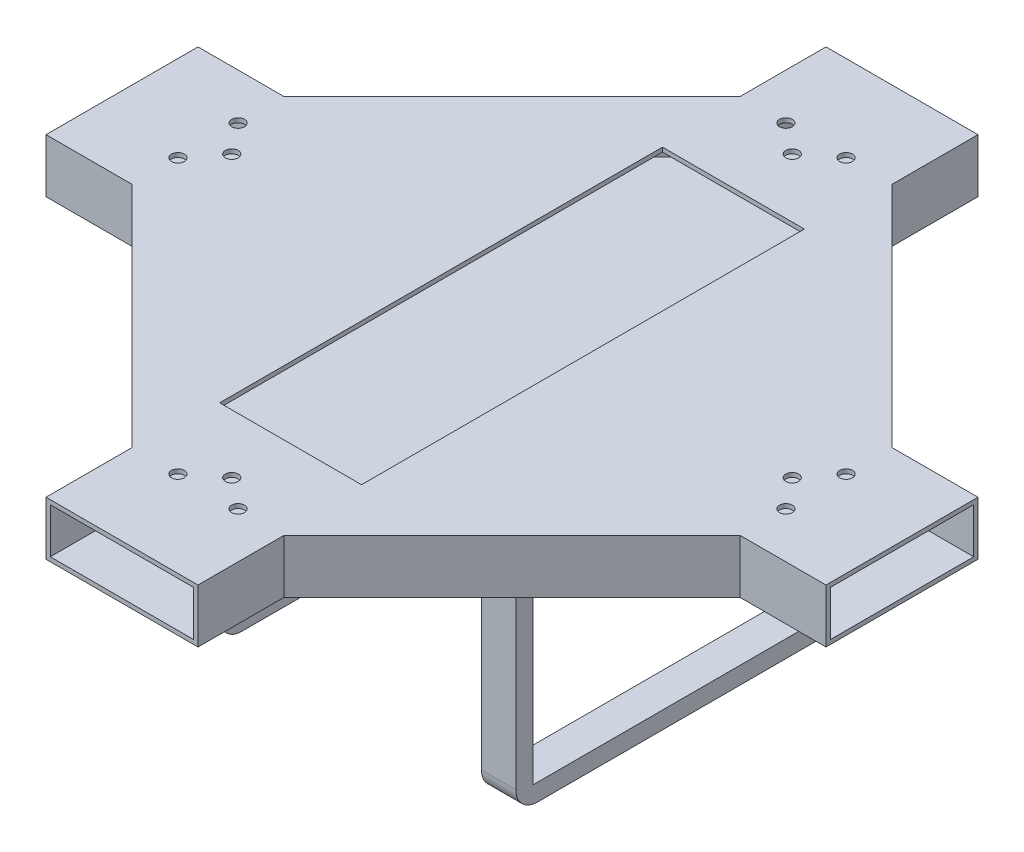
SolidWorks part; units mm, degrees
material "ABS"
ref_plane "Front Plane" through (0, 0, 0) normal (0, 0, 1) x (1, 0, 0)
ref_plane "Top Plane" through (0, 0, 0) normal (0, 1, 0) x (1, 0, 0)
ref_plane "Right Plane" through (0, 0, 0) normal (1, 0, 0) x (0, 0, -1)
sketch "Sketch1" plane through (0, 0, 0) normal (0, 1, 0) x (1, 0, 0)
  line L1 (88.3883, 0) -> (0, 88.3883)
  line L2 (0, 88.3883) -> (-88.3883, 0)
  line L3 (-88.3883, 0) -> (0, -88.3883)
  line L4 (0, -88.3883) -> (88.3883, 0)
  circle A0 centre (0, 0) radius 62.5 construction
  dimension "D1" = 125
extrude "Boss-Extrude1" add sketch "Sketch1" along normal blind 12.5
chamfer "Chamfer1" distance 25 angle 45 4 edges at (0, 6.25, 88.3883) (-88.3883, 6.25, 0) (0, 6.25, -88.3883) (88.3883, 6.25, 0)
sketch "Sketch3" plane through (0, 0, 70.7107) normal (0, 0, 1) x (1, 0, 0)
  line L4 (17.6777, 12.5) -> (-17.6777, 12.5)
  line L5 (-17.6777, 12.5) -> (-17.6777, 0)
  line L6 (-17.6777, 0) -> (17.6777, 0)
  line L7 (17.6777, 0) -> (17.6777, 12.5)
  line L8 (17.6777, 12.5) -> (-17.6777, 12.5)
  line L9 (-17.6777, 12.5) -> (-17.6777, 0)
  line L10 (-17.6777, 0) -> (17.6777, 0)
  line L11 (17.6777, 0) -> (17.6777, 12.5)
  dimension "D1" = 0
extrude "Boss-Extrude2" add sketch "Sketch3" along normal blind 20
sketch "Sketch4" plane through (70.7107, 0, 0) normal (1, 0, 0) x (0, 0, -1)
  line L4 (17.6777, 12.5) -> (-17.6777, 12.5)
  line L5 (-17.6777, 12.5) -> (-17.6777, 0)
  line L6 (-17.6777, 0) -> (17.6777, 0)
  line L7 (17.6777, 0) -> (17.6777, 12.5)
  line L8 (17.6777, 12.5) -> (-17.6777, 12.5)
  line L9 (-17.6777, 12.5) -> (-17.6777, 0)
  line L10 (-17.6777, 0) -> (17.6777, 0)
  line L11 (17.6777, 0) -> (17.6777, 12.5)
  dimension "D1" = 0
extrude "Boss-Extrude3" add sketch "Sketch4" along normal blind 20
sketch "Sketch5" plane through (0, 0, -70.7107) normal (0, 0, -1) x (-1, 0, 0)
  line L4 (17.6777, 12.5) -> (-17.6777, 12.5)
  line L5 (-17.6777, 12.5) -> (-17.6777, 0)
  line L6 (-17.6777, 0) -> (17.6777, 0)
  line L7 (17.6777, 0) -> (17.6777, 12.5)
  line L8 (17.6777, 12.5) -> (-17.6777, 12.5)
  line L9 (-17.6777, 12.5) -> (-17.6777, 0)
  line L10 (-17.6777, 0) -> (17.6777, 0)
  line L11 (17.6777, 0) -> (17.6777, 12.5)
  dimension "D1" = 0
extrude "Boss-Extrude4" add sketch "Sketch5" along normal blind 20
sketch "Sketch6" plane through (-70.7107, 0, 0) normal (-1, 0, 0) x (0, 0, 1)
  line L4 (17.6777, 12.5) -> (-17.6777, 12.5)
  line L5 (-17.6777, 12.5) -> (-17.6777, 0)
  line L6 (-17.6777, 0) -> (17.6777, 0)
  line L7 (17.6777, 0) -> (17.6777, 12.5)
  line L8 (17.6777, 12.5) -> (-17.6777, 12.5)
  line L9 (-17.6777, 12.5) -> (-17.6777, 0)
  line L10 (-17.6777, 0) -> (17.6777, 0)
  line L11 (17.6777, 0) -> (17.6777, 12.5)
  dimension "D1" = 0
extrude "Boss-Extrude5" add sketch "Sketch6" along normal blind 20
shell "Shell1" thickness 1 removed face at (-90.7107, 6.25, 0) removed face at (0, 6.25, 90.7107) removed face at (0, 6.25, -90.7107) removed face at (90.7107, 6.25, 0)
ref_plane "Plane1" through (-70.7107, 0, -17.6777) normal (0, 1, 0) x (1, 0, 0)
sketch "Sketch7" plane through (-70.7107, 0, -17.6777) normal (0, 1, 0) x (1, 0, 0)
  line L0 (63.7107, -88.3883) -> (63.7107, -108.3883) construction
  line L1 (88.3883, -108.3883) -> (53.033, -108.3883) construction
  line L2 (53.033, -88.3883) -> (63.7107, -88.3883) construction
  line L3 (53.033, -108.3883) -> (53.033, -88.3883) construction
  line L4 (63.7107, -88.3883) -> (77.7107, -88.3883) construction
  line L5 (77.7107, -88.3883) -> (88.3883, -88.3883) construction
  line L6 (88.3883, -108.3883) -> (88.3883, -88.3883) construction
  line L7 (77.7107, -88.3883) -> (77.7107, -108.3883) construction
  circle A0 centre (63.7107, -88.3883) radius 1.5
  circle A1 centre (77.7107, -88.3883) radius 1.5
  dimension "D1" = 14
  dimension "D2" = 3
  dimension "D3" = 20
extrude "Cut-Extrude1" cut sketch "Sketch7" along normal blind 20
ref_axis "Axis1" through (0, 0, 0) along (0, 1, 0)
pattern_circular "CirPattern1" count 4 over 360 about axis through (0, 0, 0) along (0, 1, 0) of "Cut-Extrude1"
sketch "Sketch8" plane through (0, 0, 0) normal (0, -1, 0) x (1, 0, 0)
  line L0 (0, 0) -> (-30.3883, 0) construction
  line L1 (-38.3883, 37.5) -> (-30.3883, 37.5)
  line L2 (-38.3883, 37.5) -> (-38.3883, -37.5)
  line L3 (-38.3883, -37.5) -> (-30.3883, -37.5)
  line L4 (-30.3883, 37.5) -> (-30.3883, -37.5)
  line L5 (30.3883, 37.5) -> (38.3883, 37.5)
  line L6 (30.3883, 37.5) -> (30.3883, -37.5)
  line L7 (30.3883, -37.5) -> (38.3883, -37.5)
  line L8 (38.3883, 37.5) -> (38.3883, -37.5)
  line L9 (0, 0) -> (30.3883, 0) construction
  line L10 (-34.3883, 37.5) -> (-34.3883, 54) construction
  line L11 (-70.7107, 17.6777) -> (-17.6777, 70.7107) construction
  line L12 (-34.3883, -37.5) -> (-34.3883, -54) construction
  line L13 (-17.6777, -70.7107) -> (-70.7107, -17.6777) construction
  dimension "D1" = 75
  dimension "D2" = 8
  dimension "D3" = 16.5
extrude "Boss-Extrude6" add sketch "Sketch8" along normal blind 50
sketch "Sketch9" plane through (38.3883, 0, 0) normal (1, 0, 0) x (0, 0, -1)
  line L0 (33.5, -4) -> (-33.5, -4)
  line L1 (-33.5, -4) -> (-33.5, -46)
  line L2 (-33.5, -46) -> (33.5, -46)
  line L3 (33.5, -46) -> (33.5, -4)
  line L4 (37.5, 0) -> (-37.5, 0)
  line L5 (-37.5, 0) -> (-37.5, -50)
  line L6 (-37.5, -50) -> (37.5, -50)
  line L7 (37.5, -50) -> (37.5, 0)
  line L8 (37.5, 0) -> (-37.5, 0) construction
  line L9 (-37.5, 0) -> (-37.5, -50) construction
  line L10 (-37.5, -50) -> (37.5, -50) construction
  line L11 (37.5, -50) -> (37.5, 0) construction
  dimension "D1" = 0
  dimension "D2" = 4
extrude "Cut-Extrude2" cut sketch "Sketch9" against normal up to surface (76.7767 mm away) up to face at (-38.3883, -25, 0)
fillet "Fillet2" radius 5 8 edges at (34.3883, 0, -37.5) (38.3883, 0, 0) (34.3883, 0, 37.5) (30.3883, 0, 0) (-34.3883, 0, 37.5) (-38.3883, 0, 0) (-34.3883, 0, -37.5) (-30.3883, 0, 0)
fillet "Fillet3" radius 5 4 edges at (-34.3883, -50, -37.5) (-34.3883, -50, 37.5) (34.3883, -50, 37.5) (34.3883, -50, -37.5)
sketch "Sketch10" plane through (0, 12.5, 0) normal (0, 1, 0) x (1, 0, 0)
  line L1 (-16.5, 51.5) -> (16.5, 51.5)
  line L2 (-16.5, 51.5) -> (-16.5, -51.5)
  line L3 (-16.5, -51.5) -> (16.5, -51.5)
  line L4 (16.5, 51.5) -> (16.5, -51.5)
  line L5 (-16.5, 51.5) -> (16.5, -51.5) construction
  line L6 (-16.5, -51.5) -> (16.5, 51.5) construction
  point P0 (0, 0)
  dimension "D1" = 33
  dimension "D2" = 103
extrude "Cut-Extrude3" cut sketch "Sketch10" against normal up to next
sketch "Sketch11" plane through (0, 12.5, 0) normal (0, 1, 0) x (1, 0, 0)
  line L0 (0, 0) -> (0, -65.1819) construction
  circle A0 centre (0, -65.1819) radius 1.5
  circle A1 centre (-65.1819, 0) radius 1.5
  circle A2 centre (0, 65.1819) radius 1.5
  circle A3 centre (65.1819, 0) radius 1.5
  point P13 (0, 0)
  dimension "D1" = 3
  dimension "D2" = 4
extrude "Cut-Extrude4" cut sketch "Sketch11" against normal up to surface (12.5 mm away) up to face at (34.3883, 0, 0)
